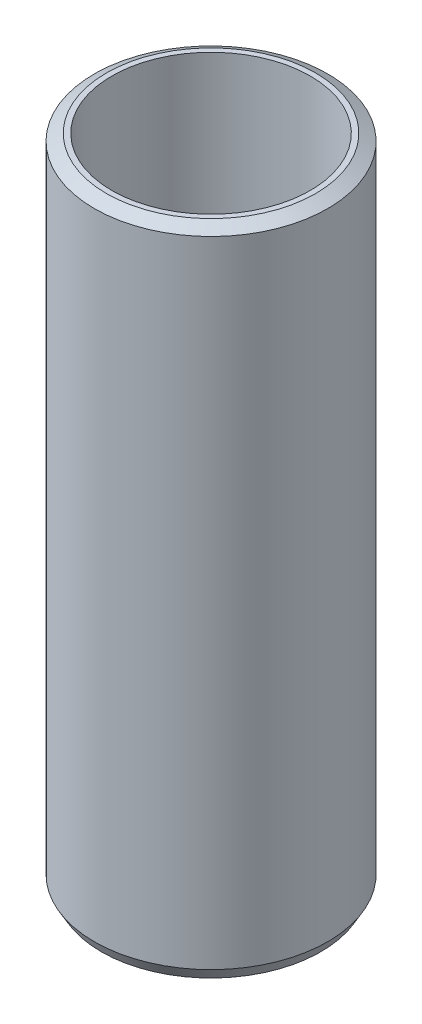
SolidWorks part; units mm, degrees
ref_plane "Front Plane" through (0, 0, 0) normal (0, 0, 1) x (1, 0, 0)
ref_plane "Top Plane" through (0, 0, 0) normal (0, 1, 0) x (1, 0, 0)
ref_plane "Right Plane" through (0, 0, 0) normal (1, 0, 0) x (0, 0, -1)
sketch "Sketch1" plane through (0, 0, 0) normal (0, 1, 0) x (1, 0, 0)
  circle A0 centre (0, 0) radius 55
  dimension "SHAFT_OD" = 110
extrude "Boss-Extrude1" add sketch "Sketch1" along normal blind 308.2057
sketch "Sketch2" plane through (0, 0, 0) normal (0, 1, 0) x (1, 0, 0)
  circle A0 centre (0, 0) radius 46.7583
  dimension "BORE_D" = 93.5165
extrude "Cut-Extrude1" cut sketch "Sketch2" along normal through all
chamfer "Chamfer1" distance 3.2553 angle 60.4 2 edges at (0, 308.2057, 55) (0, 0, 55) first distance on face at (0, 308.2057, 55) first distance on face at (0, 0, 46.7583)
